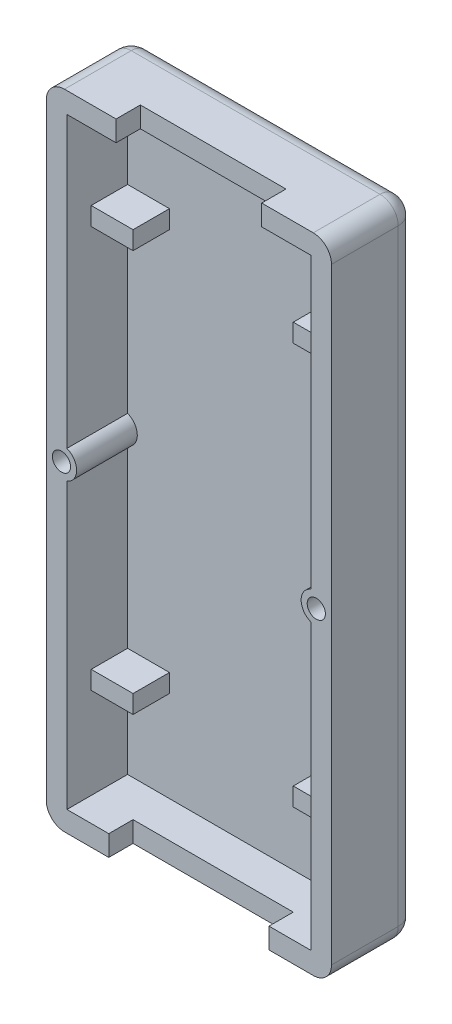
SolidWorks part; units mm, degrees
ref_plane "前视基准面" through (0, 0, 0) normal (0, 0, 1) x (1, 0, 0)
ref_plane "上视基准面" through (0, 0, 0) normal (0, 1, 0) x (1, 0, 0)
ref_plane "右视基准面" through (0, 0, 0) normal (1, 0, 0) x (0, 0, -1)
sketch "草图1" plane through (0, 0, 0) normal (0, 0, 1) x (1, 0, 0)
  line L1 (0, 0) -> (23.5, 0)
  line L2 (0, 0) -> (0, -53)
  line L3 (0, -53) -> (23.5, -53)
  line L4 (23.5, 0) -> (23.5, -53)
  line L5 (1.7, -1.7) -> (21.8, -1.7)
  line L6 (1.7, -1.7) -> (1.7, -51.3)
  line L7 (1.7, -51.3) -> (21.8, -51.3)
  line L8 (21.8, -1.7) -> (21.8, -51.3)
  circle A0 centre (1.25, -26.7) radius 1.25
  circle A1 centre (22.25, -26.7) radius 1.25
  dimension "D7" = 2.5
  dimension "D8" = 2.5
  dimension "D10" = 25
  dimension "D1" = 23.5
  dimension "D2" = 53
  dimension "D3" = 1.7
  dimension "D4" = 1.7
  dimension "D5" = 1.7
  dimension "D6" = 1.7
  dimension "D9" = 25
extrude "凸台-拉伸1" add sketch "草图1" along normal blind 7 contours A1 L8 L7 L6 A0 L2 L3 L4 | L6 A0 | A1 L4 L1 L2 A0 L6 L5 L8 | A1 L8 | A1 | A0 region at (11.75, -0.3557, 0) region at (0.3434, -28.0216, 0) region at (0.9525, -26.7, 0) region at (22.5475, -26.7, 0)
extrude "凸台-拉伸2" add sketch "草图1<2>" along normal blind 2 contours L8 L5 L6 L7 region at (11.75, -26.4995, 0)
sketch "草图1<2>" plane through (0, 0, 0) normal (0, 0, 1) x (1, 0, 0) same geometry as "草图1"
sketch "草图2" plane through (0, 0, 2) normal (0, 0, 1) x (1, 0, 0)
  line L0 (1.7, -1.7) -> (1.7, -25.5338) construction
  line L1 (1.7, -42.3) -> (5.15, -42.3)
  line L2 (1.7, -42.3) -> (1.7, -43.8)
  line L3 (1.7, -43.8) -> (5.15, -43.8)
  line L4 (5.15, -42.3) -> (5.15, -43.8)
  line L6 (21.8, -43.8) -> (18.35, -43.8)
  line L7 (21.8, -43.8) -> (21.8, -42.3)
  line L8 (21.8, -42.3) -> (18.35, -42.3)
  line L9 (18.35, -43.8) -> (18.35, -42.3)
  line L10 (1.7, -51.3) -> (21.8, -51.3) construction
  line L11 (1.7, -9.2) -> (5.15, -9.2)
  line L12 (1.7, -9.2) -> (1.7, -10.7)
  line L13 (1.7, -10.7) -> (5.15, -10.7)
  line L14 (5.15, -9.2) -> (5.15, -10.7)
  line L15 (21.8, -10.7) -> (18.35, -10.7)
  line L16 (21.8, -10.7) -> (21.8, -9.2)
  line L17 (21.8, -9.2) -> (18.35, -9.2)
  line L18 (18.35, -10.7) -> (18.35, -9.2)
  line L20 (1.7, -1.7) -> (21.8, -1.7) construction
  line L21 (21.8, -1.7) -> (21.8, -25.5338) construction
  line L22 (21.8, -27.8662) -> (21.8, -51.3) construction
  dimension "D1" = 13.2
  dimension "D2" = 7.5
  dimension "D3" = 7.5
  dimension "D4" = 1.5
  dimension "D5" = 1.5
  dimension "D6" = 3.45
  dimension "D7" = 7.5
  dimension "D8" = 0
  dimension "D9" = 3.45
  dimension "D10" = 3.45
  dimension "D11" = 13.2
  dimension "D12" = 7.5
  dimension "D14" = 1.5
  dimension "D15" = 1.5
extrude "凸台-拉伸3" add sketch "草图2" along normal blind 3
sketch "草图3" plane through (0, 0, 7) normal (0, 0, 1) x (1, 0, 0)
  line L0 (1.7, -51.3) -> (21.8, -51.3) construction
  line L1 (5.15, -51.3) -> (18.35, -51.3)
  line L2 (5.15, -51.3) -> (5.15, -53)
  line L3 (5.15, -53) -> (18.35, -53)
  line L4 (18.35, -51.3) -> (18.35, -53)
  line L5 (0, -53) -> (23.5, -53) construction
  line L6 (0, 0) -> (23.5, 0) construction
  line L7 (5.75, 0) -> (17.75, 0)
  line L8 (5.75, 0) -> (5.75, -1.7)
  line L9 (5.75, -1.7) -> (17.75, -1.7)
  line L10 (17.75, 0) -> (17.75, -1.7)
  line L11 (1.7, -1.7) -> (21.8, -1.7) construction
  line L12 (0, 0) -> (0, -53) construction
  circle A0 centre (22.25, -26.7) radius 0.75
  circle A3 centre (1.25, -26.7) radius 0.75
  dimension "D1" = 1.5
  dimension "D2" = 1.5
  dimension "D3" = 13.2
  dimension "D4" = 12
  dimension "D5" = 5.75
  dimension "D6" = 5.15
extrude "切除-拉伸1" cut sketch "草图3" against normal blind 2
fillet "圆角1" radius 1.5 4 edges at (0, 0, 3.5) (23.5, 0, 3.5) (23.5, -53, 3.5) (0, -53, 3.5)
fillet "圆角2" radius 1.5 8 edges at (0.4393, -0.4393, 0) (11.75, 0, 0) (23.0607, -0.4393, 0) (23.5, -26.5, 0) (23.0607, -52.5607, 0) (11.75, -53, 0) (0.4393, -52.5607, 0) (0, -26.5, 0)
